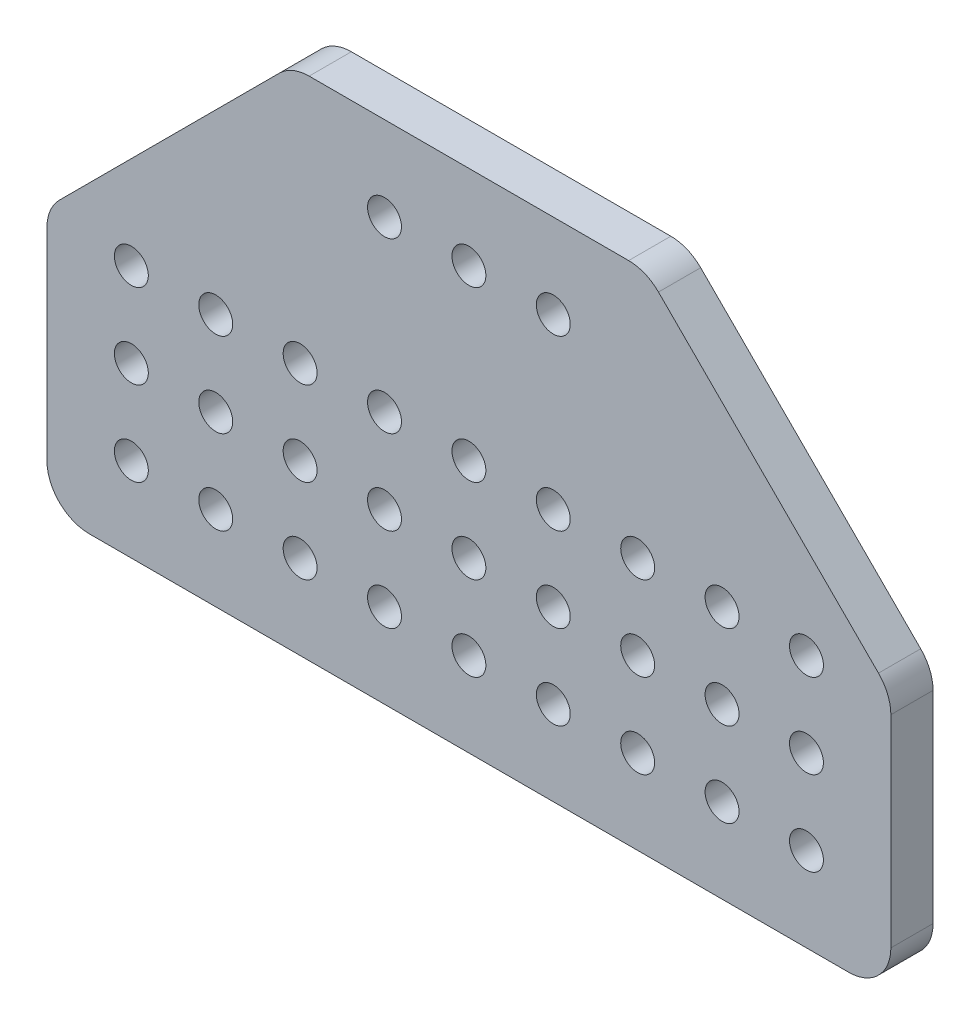
SolidWorks part; units mm, degrees
material "6061-T6 (SS)"
ref_plane "Front Plane" through (0, 0, 0) normal (0, 0, 1) x (1, 0, 0)
ref_plane "Top Plane" through (0, 0, 0) normal (0, 1, 0) x (1, 0, 0)
ref_plane "Right Plane" through (0, 0, 0) normal (1, 0, 0) x (0, 0, -1)
sketch "Sketch1" plane through (0, 0, 0) normal (0, 0, 1) x (1, 0, 0)
  line L1 (0, 0) -> (127, 0)
  line L2 (0, 0) -> (0, 82.55)
  line L3 (0, 82.55) -> (127, 82.55)
  line L4 (127, 0) -> (127, 82.55)
  dimension "D1" = 82.55
  dimension "D2" = 127
extrude "Boss-Extrude1" add sketch "Sketch1" along normal blind 6.35
sketch "Sketch2" plane through (0, 0, 0) normal (0, 0, -1) x (-1, 0, 0)
  line L0 (-127, 82.55) -> (0, 82.55) construction
  line L1 (0, 82.55) -> (0, 0) construction
  circle A0 centre (-76.2, 63.5) radius 2.5527
  circle A1 centre (-63.5, 63.5) radius 2.5527
  circle A2 centre (-50.8, 63.5) radius 2.5527
  point P2 (0, 0)
  dimension "D2" = 12.7
  dimension "D3" = 12.7
  dimension "D4" = 50.8
  dimension "D5" = 19.05
  dimension "D7" = 5.1054
  dimension "D8" = 5.1054
  dimension "D9" = 5.1054
extrude "Cut-Extrude1" cut sketch "Sketch2" against normal through all and the other way through all
sketch "Sketch3" plane through (0, 0, 0) normal (0, 0, -1) x (-1, 0, 0)
  line L0 (-127, 0) -> (-127, 82.55) construction
  line L1 (0, 0) -> (-127, 0) construction
  circle A0 centre (-114.3, 38.1) radius 2.5527
  circle A1 centre (-114.3, 25.4) radius 2.5527
  circle A2 centre (-114.3, 12.7) radius 2.5527
  circle A3 centre (-101.6, 38.1) radius 2.5527
  circle A4 centre (-101.6, 25.4) radius 2.5527
  circle A5 centre (-101.6, 12.7) radius 2.5527
  circle A6 centre (-88.9, 38.1) radius 2.5527
  circle A7 centre (-88.9, 25.4) radius 2.5527
  circle A8 centre (-88.9, 12.7) radius 2.5527
  circle A9 centre (-76.2, 38.1) radius 2.5527
  circle A10 centre (-76.2, 25.4) radius 2.5527
  circle A11 centre (-76.2, 12.7) radius 2.5527
  circle A12 centre (-63.5, 38.1) radius 2.5527
  circle A13 centre (-63.5, 25.4) radius 2.5527
  circle A14 centre (-63.5, 12.7) radius 2.5527
  circle A15 centre (-50.8, 38.1) radius 2.5527
  circle A16 centre (-50.8, 25.4) radius 2.5527
  circle A17 centre (-50.8, 12.7) radius 2.5527
  circle A18 centre (-38.1, 38.1) radius 2.5527
  circle A19 centre (-38.1, 25.4) radius 2.5527
  circle A20 centre (-38.1, 12.7) radius 2.5527
  circle A21 centre (-25.4, 38.1) radius 2.5527
  circle A22 centre (-25.4, 25.4) radius 2.5527
  circle A23 centre (-25.4, 12.7) radius 2.5527
  circle A24 centre (-12.7, 38.1) radius 2.5527
  circle A25 centre (-12.7, 25.4) radius 2.5527
  circle A26 centre (-12.7, 12.7) radius 2.5527
  dimension "D1" = 5.1054
  dimension "D2" = 5.1054
  dimension "D3" = 5.1054
  dimension "D4" = 12.7
  dimension "D5" = 12.7
  dimension "D6" = 12.7
  dimension "D7" = 12.7
  dimension "D8" = 12.7
  dimension "D9" = 12.7
  dimension "D11" = 12.7
  dimension "D10" = 9
extrude "Cut-Extrude2" cut sketch "Sketch3" against normal through all
sketch "Sketch4" plane through (0, 0, 0) normal (0, 0, -1) x (-1, 0, 0)
  line L0 (-83.82, 82.55) -> (-127, 39.37)
  line L1 (-127, 82.55) -> (0, 82.55) construction
  line L2 (-127, 39.37) -> (-127, 82.55)
  line L3 (-127, 82.55) -> (-83.82, 82.55)
  line L4 (-43.18, 82.55) -> (0, 82.55)
  line L5 (0, 82.55) -> (0, 39.37)
  line L6 (0, 82.55) -> (0, 0) construction
  line L7 (0, 39.37) -> (-43.18, 82.55)
  dimension "D1" = 45
  dimension "D2" = 45
  dimension "D3" = 43.18
  dimension "D4" = 43.18
extrude "Cut-Extrude3" cut sketch "Sketch4" against normal through all
sketch "Sketch5" plane through (0, 0, 0) normal (0, 0, -1) x (-1, 0, 0)
  line L0 (-90.17, 76.2) -> (-36.83, 76.2)
  line L1 (-127, 39.37) -> (-83.82, 82.55) construction
  line L2 (-43.18, 82.55) -> (0, 39.37) construction
  line L3 (-36.83, 76.2) -> (-43.18, 82.55)
  line L4 (-43.18, 82.55) -> (-83.82, 82.55)
  line L5 (-83.82, 82.55) -> (-90.17, 76.2)
  dimension "D1" = 6.35
extrude "Cut-Extrude4" cut sketch "Sketch5" against normal through all
fillet "Fillet1" radius 6.35 6 edges at (127, 39.37, 3.175) (127, 0, 3.175) (0, 0, 3.175) (36.83, 76.2, 3.175) (90.17, 76.2, 3.175) (0, 39.37, 3.175)
